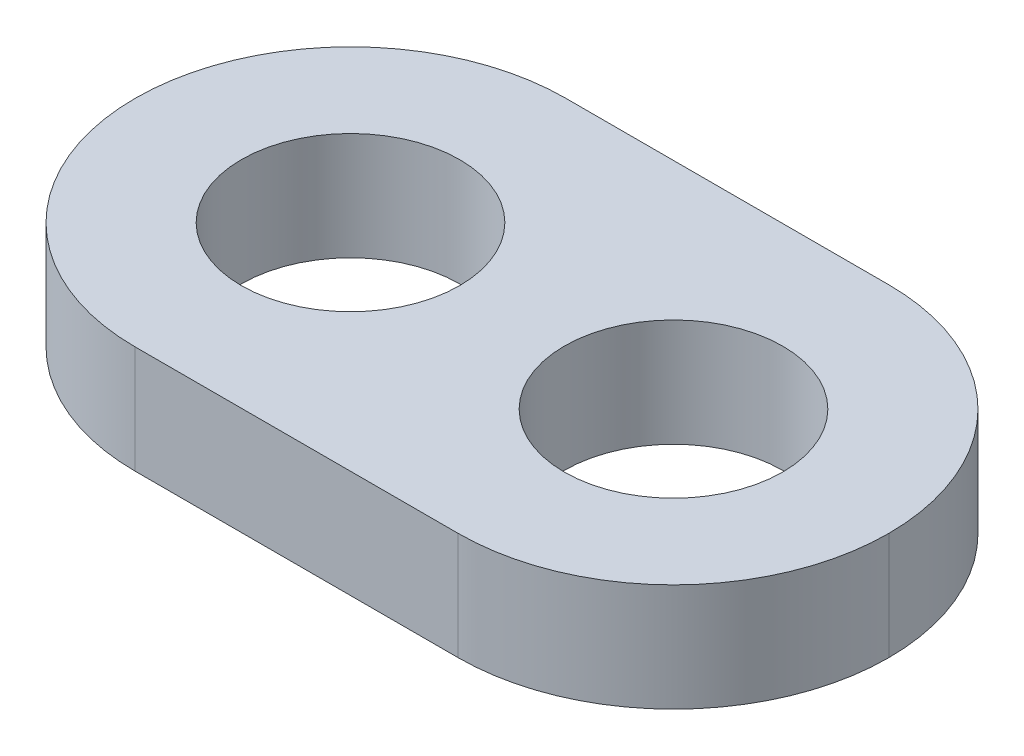
SolidWorks part; units mm, degrees
ref_plane "Front Plane" through (0, 0, 0) normal (0, 0, 1) x (1, 0, 0)
ref_plane "Top Plane" through (0, 0, 0) normal (0, 1, 0) x (1, 0, 0)
ref_plane "Right Plane" through (0, 0, 0) normal (1, 0, 0) x (0, 0, -1)
sketch "Sketch1" plane through (0, 0, 0) normal (0, 1, 0) x (1, 0, 0)
  line L0 (0, 10) -> (0, -10) construction
  line L1 (-17.5, 10) -> (17.5, 10)
  line L2 (-17.5, 10) -> (-17.5, -10)
  line L3 (-17.5, -10) -> (17.5, -10)
  line L4 (17.5, 10) -> (17.5, -10)
  circle A1 centre (-7.5, 0) radius 5.07
  circle A2 centre (7.5, 0) radius 5.07
  point P0 (0, 10)
  point P7 (-17.5, 0)
  point P12 (0, 0)
  dimension "D1" = 10
  dimension "D2" = 15
  dimension "D3" = 10.14
  dimension "D4" = 10
extrude "Boss-Extrude1" add sketch "Sketch1" along normal blind 5
fillet "Fillet1" radius 10 4 edges at (-17.5, 2.5, -10) (17.5, 2.5, -10) (17.5, 2.5, 10) (-17.5, 2.5, 10)
